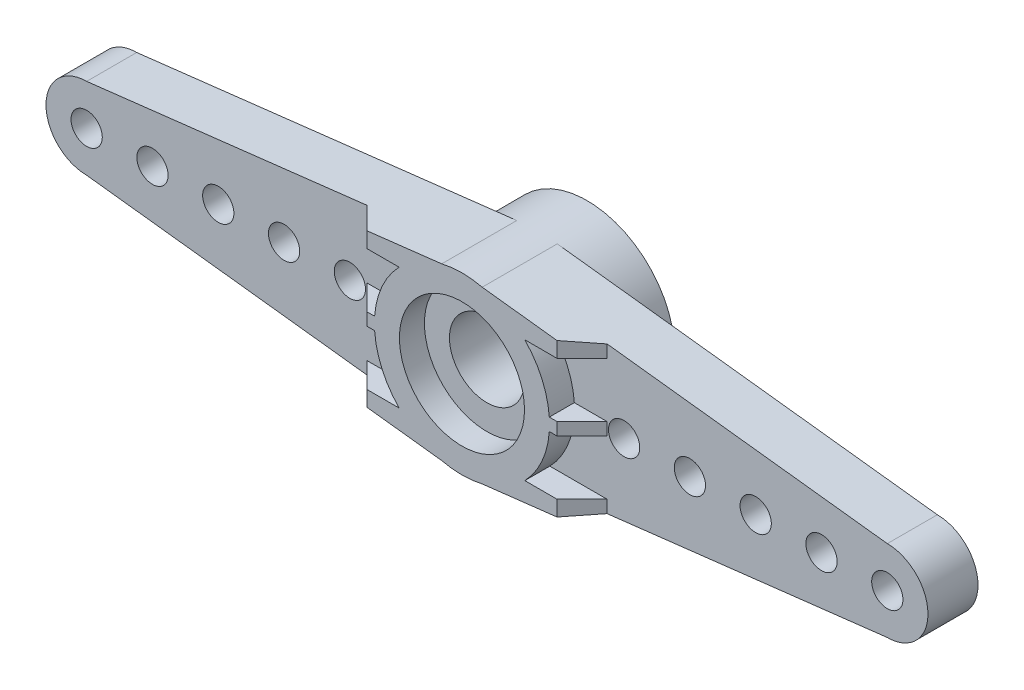
SolidWorks part; units mm, degrees
ref_plane "Спереди" through (0, 0, 0) normal (0, 0, 1) x (1, 0, 0)
ref_plane "Сверху" through (0, 0, 0) normal (0, 1, 0) x (1, 0, 0)
ref_plane "Справа" through (0, 0, 0) normal (1, 0, 0) x (0, 0, -1)
sketch "Эскиз1" plane through (0, 0, 0) normal (0, 0, 1) x (1, 0, 0)
  circle A0 centre (0, 0) radius 3.5
  circle A1 centre (0, 0) radius 2.5
  dimension "D1" = 7
  dimension "D2" = 5
extrude "Бобышка-Вытянуть1" add sketch "Эскиз1" along normal blind 5
sketch "Эскиз2" plane through (0, 0, 5) normal (0, 0, 1) x (1, 0, 0)
  line L0 (-16, 1.625) -> (0, 3.5)
  line L1 (-16, -1.625) -> (0, -3.5)
  line L2 (0, -2.75) -> (0, 2.75) construction
  line L3 (16, -1.625) -> (0, -3.5)
  line L4 (16, 1.625) -> (0, 3.5)
  circle A0 centre (0, 0) radius 1.5
  circle A1 centre (-16, 0) radius 1.625
  circle A2 centre (0, 0) radius 3.5 construction
  circle A3 centre (-16, 0) radius 0.625
  circle A4 centre (-13.37, 0) radius 0.625
  circle A5 centre (-10.74, 0) radius 0.625
  circle A6 centre (-8.11, 0) radius 0.625
  circle A7 centre (-5.48, 0) radius 0.625
  circle A8 centre (5.48, 0) radius 0.625
  circle A9 centre (8.11, 0) radius 0.625
  circle A10 centre (10.74, 0) radius 0.625
  circle A11 centre (13.37, 0) radius 0.625
  circle A12 centre (16, 0) radius 0.625
  circle A13 centre (16, 0) radius 1.625
  circle M6 centre (0, 0) radius 3.5
  circle M7 centre (0, 0) radius 2.5
  dimension "D1" = 3
  dimension "D2" = 3.25
  dimension "D4" = 1.25
  dimension "D3" = 16
  dimension "D5" = 5
extrude "Бобышка-Вытянуть2" add sketch "Эскиз2" against normal blind 2 from offset 1 contours A1 L1 L0 A7 A6 A5 A4 M6 | A1 A3 | L3 A13 L4 A10 A8 A9 A11 M6 | A13 A12 | A0 M7 region at (-8.3852, 2.3497, 5) region at (-14.8835, 1.1165, 5) region at (8.3852, 2.3497, 5) region at (17.1165, 1.1165, 5) region at (-2.4293, 0, 5) offset against normal yes
sketch "Эскиз3" plane through (0, 0, 4) normal (0, 0, 1) x (1, 0, 0)
  line L0 (-0.8092, 3.4052) -> (-4.8, 2.9375)
  line L1 (-16, 1.625) -> (-0.8092, 3.4052) construction
  line L2 (-4.8, 2.4375) -> (-2.5117, 2.4375)
  line L3 (-4.8, 2.9375) -> (-4.8, 2.4375)
  line L4 (2.75, 0) -> (-2.75, 0) construction
  line L5 (-3.4911, 0.25) -> (-4.8, 0.25)
  line L6 (-3.4911, 0.25) -> (-3.4911, -0.25)
  line L7 (-3.4911, -0.25) -> (-4.8, -0.25)
  line L8 (-4.8, 0.25) -> (-4.8, -0.25)
  line L9 (-4.8, -2.9375) -> (-4.8, -2.4375)
  line L10 (-4.8, -2.4375) -> (-2.5117, -2.4375)
  line L11 (-0.8092, -3.4052) -> (-4.8, -2.9375)
  line L12 (0, -2.75) -> (0, 2.75) construction
  line L13 (0.8092, -3.4052) -> (4.8, -2.9375)
  line L14 (4.8, -2.4375) -> (2.5117, -2.4375)
  line L15 (4.8, -2.9375) -> (4.8, -2.4375)
  line L16 (4.8, 0.25) -> (4.8, -0.25)
  line L17 (3.4911, -0.25) -> (4.8, -0.25)
  line L18 (3.4911, 0.25) -> (3.4911, -0.25)
  line L19 (3.4911, 0.25) -> (4.8, 0.25)
  line L20 (4.8, 2.9375) -> (4.8, 2.4375)
  line L21 (4.8, 2.4375) -> (2.5117, 2.4375)
  line L22 (0.8092, 3.4052) -> (4.8, 2.9375)
  circle A0 centre (0, 0) radius 3.5 construction
  arc A1 (-0.8092, 3.4052) -> (-0.8092, -3.4052) centre (0, 0) ccw construction
  circle A2 centre (0, 0) radius 3.5
  point P17 (-4.8, 0)
  line M7 (-0.8092, 3.4052) -> (-16, 1.625)
  line M9 (-16, -1.625) -> (-0.8092, -3.4052)
  arc M10 (-0.8092, -3.4052) -> (-0.8092, 3.4052) centre (0, 0) cw
  dimension "D1" = 0.5
  dimension "D2" = 4.8
extrude "Бобышка-Вытянуть3" add sketch "Эскиз3" along normal blind 1 contours L3 L2 M7 M10 | L5 L8 L7 M10 | L10 L9 M9 M10 | A2 L13 L15 L14 | A2 L17 L16 L19 | A2 L21 L20 L22 region at (-3.2001, 2.8266, 4) region at (3.2001, 2.8266, 4) region at (-4.1485, 0, 4) region at (4.1485, 0, 4) region at (-3.2001, -2.8266, 4) region at (3.2001, -2.8266, 4)
chamfer "Фаска1" distance 1 angle 45 6 edges at (4.8, 2.6875, 5) (4.8, 0, 5) (4.8, -2.6875, 5) (-4.8, -2.6875, 5) (-4.8, 0, 5) (-4.8, 2.6875, 5)
